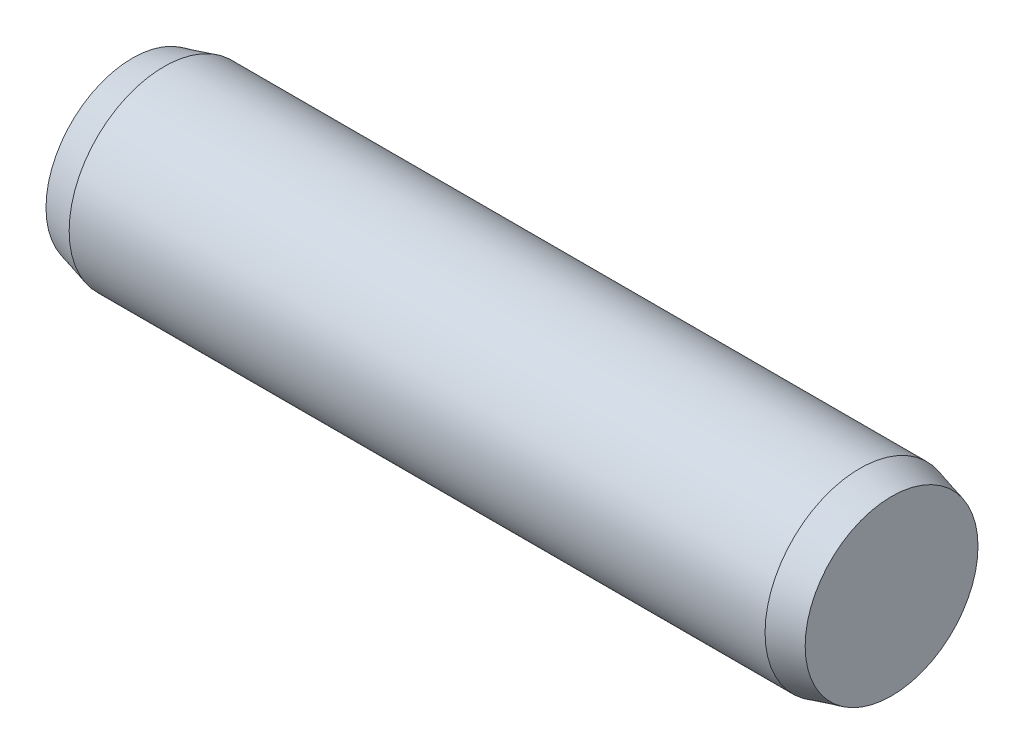
SolidWorks part; units mm, degrees
ref_plane "Front Plane" through (0, 0, 0) normal (0, 0, 1) x (1, 0, 0)
ref_plane "Top Plane" through (0, 0, 0) normal (0, 1, 0) x (1, 0, 0)
ref_plane "Right Plane" through (0, 0, 0) normal (1, 0, 0) x (0, 0, -1)
sketch "Sketch1" plane through (0, 0, 0) normal (0, 0, 1) x (1, 0, 0)
  line L0 (-5.5, 0) -> (5.5, 0) construction
  line L1 (5.5, 1.5) -> (5.5, -1.5) construction
  line L2 (-5.5, 1.5) -> (-5.5, -1.5) construction
  line L3 (6, 1.5) -> (6, -1.5) construction
  line L4 (-6, 1.5) -> (-6, -1.5) construction
  line L5 (-5.5, 0) -> (-6, 0) construction
  line L6 (5.5, 0) -> (6, 0) construction
  dimension "Dia" = 3
  dimension "C" = 0.5
  dimension "D1" = 0.5
  dimension "Length" = 12
sketch "Sketch2" plane through (0, 0, 0) normal (1, 0, 0) x (0, 0, -1)
  circle A0 centre (0, 0) radius 1.5
extrude "Extrude1" add sketch "Sketch2" against normal up to vertex (5.5 mm away) and the other way up to vertex (5.5 mm away) up to point (-5.5, 1.5, 0) other way up to point (5.5, 1.5, 0)
sketch "Sketch3" plane through (5.5, 0, 0) normal (1, 0, 0) x (0, 0, -1)
  circle A1 centre (0, 0) radius 1.5
  circle A2 centre (0, 0) radius 1.5
  dimension "D1" = 0
extrude "Extrude2" add sketch "Sketch3" along normal up to vertex (0.5 mm away) draft 15 up to point (6, 0, 0)
sketch "Sketch4" plane through (-5.5, 0, 0) normal (-1, 0, 0) x (0, 0, 1)
  circle A1 centre (0, 0) radius 1.5
  circle A2 centre (0, 0) radius 1.5
  dimension "D1" = 0
extrude "Extrude3" add sketch "Sketch4" along normal up to vertex (0.5 mm away) draft 15 up to point (-6, 0, 0)
equation "\"D1@Sketch1\" = \"C@Sketch1\""
